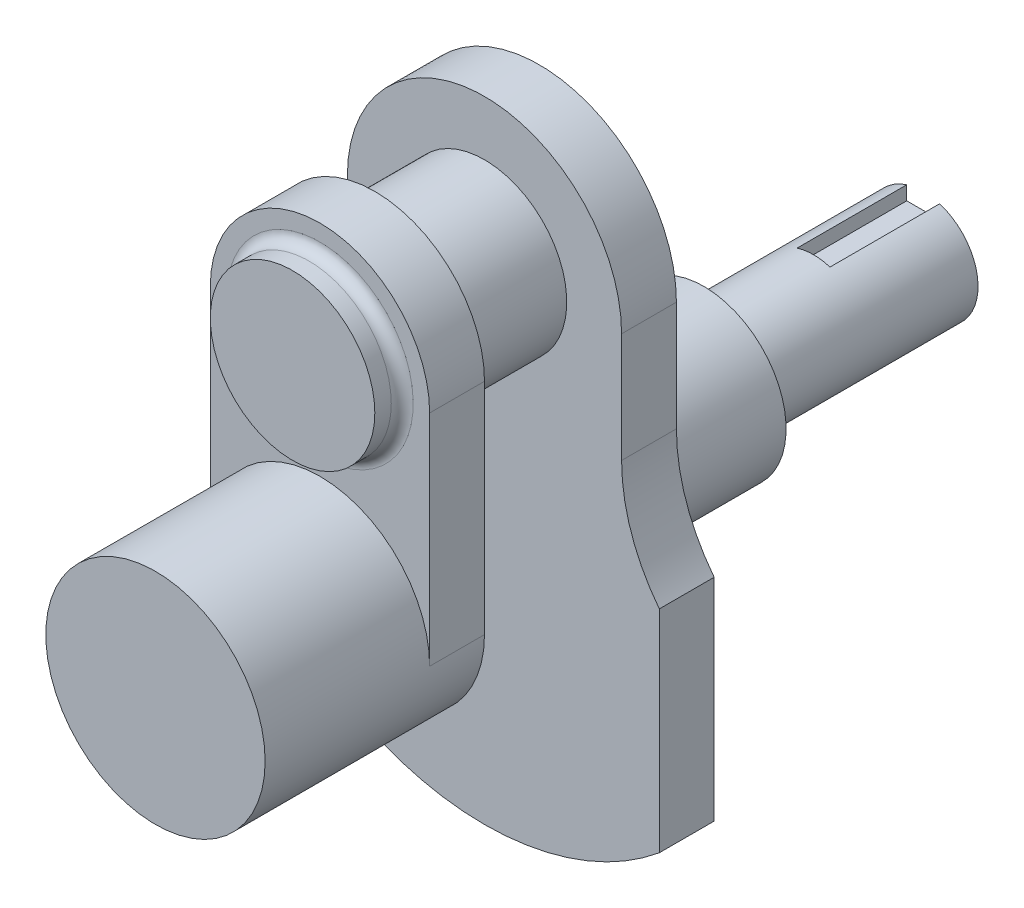
SolidWorks part; units mm, degrees
ref_plane "Ön Düzlem" through (0, 0, 0) normal (0, 0, 1) x (1, 0, 0)
ref_plane "Üst Düzlem" through (0, 0, 0) normal (0, 1, 0) x (1, 0, 0)
ref_plane "Sağ Düzlem" through (0, 0, 0) normal (1, 0, 0) x (0, 0, -1)
sketch "Çizim1" plane through (0, 0, 0) normal (0, 0, 1) x (1, 0, 0)
  line L0 (0, 0) -> (-40, 0)
  line L1 (-40, 0) -> (-40, 40)
  line L2 (-40, 40) -> (0, 40)
  line L3 (0, 40) -> (0, 0)
  dimension "D1" = 40
  dimension "D2" = 40
extrude "Yükseklik-Ekstrüzyon1" add sketch "Çizim1" along normal mid plane 40
sketch "Çizim3" plane through (0, 0, 20) normal (0, 0, 1) x (1, 0, 0)
  line L0 (-20, 40) -> (-20, 0) construction
  line L1 (0, 40) -> (-40, 40) construction
  line L2 (-40, 0) -> (0, 0) construction
  line L3 (0, 0) -> (0, 40) construction
  line L4 (-40, 40) -> (-40, 0) construction
  line L5 (-40, 0) -> (0, 0)
  line L6 (0, 0) -> (0, 40)
  line L7 (0, 40) -> (-40, 40)
  line L8 (-40, 40) -> (-40, 0)
  circle A0 centre (-20, 20) radius 20
  line M1 (0, 0) -> (0, 40)
  line M2 (0, 40) -> (-40, 40)
  line M3 (-40, 40) -> (-40, 0)
  line M4 (-40, 0) -> (0, 0)
  dimension "D1" = 40
extrude "Kes-Ekstrüzyon1" cut sketch "Çizim3" against normal blind 40 contours A0 L7 M3 | A0 L6 M2 | A0 L5 M1 | A0 L8 M4 region at (-35.5326, 4.4674, 20) region at (-4.4674, 4.4674, 20) region at (-35.5326, 35.5326, 20) region at (-4.4674, 35.5326, 20)
sketch "Çizim4" plane through (0, 0, 0) normal (1, 0, 0) x (0, 0, -1)
  line L0 (-20, 20) -> (20, 20) construction
  line L1 (-20, 40) -> (-20, 0) construction
  line L2 (20, 0) -> (20, 40) construction
  line L3 (10, 20) -> (10, 85)
  line L4 (10, 85) -> (20, 85)
  line L5 (20, 85) -> (20, 20)
  line L6 (10, 20) -> (20, 20)
  dimension "D1" = 10
  dimension "D2" = 65
extrude "Yükseklik-Ekstrüzyon2" add sketch "Çizim4" against normal blind 40
sketch "Çizim7" plane through (0, 0, -10) normal (0, 0, 1) x (1, 0, 0)
  line L0 (-20, 20) -> (-20, 60) construction
  line L1 (-40, 60) -> (0, 60) construction
  line L2 (0, 85) -> (0, 20) construction
  line L3 (-40, 85) -> (0, 85) construction
  line L4 (-40, 85) -> (-40, 20) construction
  line L5 (0, 85) -> (0, 20)
  line L6 (-40, 85) -> (0, 85)
  line L7 (-40, 85) -> (-40, 20)
  circle A0 centre (-20, 20) radius 20 construction
  arc A1 (0, 20) -> (-40, 20) centre (-20, 20) ccw construction
  circle A2 centre (-20, 20) radius 20
  arc A3 (0, 20) -> (-40, 20) centre (-20, 20) ccw
  circle A4 centre (-20, 60) radius 20
  line M2 (-40, 85) -> (-40, 20)
  line M5 (0, 85) -> (-40, 85)
  dimension "D2" = 40
  dimension "D1" = 40
extrude "Kes-Ekstrüzyon2" cut sketch "Çizim7" against normal blind 40 contours A4 L5 M5 M2 region at (-0.4717, 72.5, -10)
sketch "Çizim8" plane through (0, 0, -10) normal (0, 0, 1) x (1, 0, 0)
  circle A0 centre (-20, 60) radius 15
  dimension "D1" = 30
extrude "Yükseklik-Ekstrüzyon3" add sketch "Çizim8" along normal blind 5 and the other way blind 30
fillet "Radyus1" radius 2 1 edges at (-20, 45, -10)
sketch "Çizim10" plane through (0, 0, -40) normal (0, 0, -1) x (-1, 0, 0)
  line L0 (-5, 60) -> (45, 60)
  line L1 (20, 60) -> (20, 20) construction
  line L2 (-5, 60) -> (-5, 40)
  line L3 (45, 60) -> (45, 40)
  line L4 (20, 20) -> (-37.5, 20) construction
  line L5 (-37.5, 20) -> (-37.5, 40) construction
  line L6 (20, 20) -> (-20, 20) construction
  line L7 (-20, 20) -> (-20, 40) construction
  line L8 (-20, 40) -> (-5, 40) construction
  line L9 (-11.8826, 20) -> (-11.8826, -18.5162)
  line L10 (51.8826, 20) -> (51.8826, -18.5162)
  arc A0 (45, 60) -> (-5, 60) centre (20, 60) ccw
  arc A1 (-11.8826, 20) -> (-5, 40) centre (-37.5, 40) ccw
  arc A2 (-11.8826, -18.5162) -> (51.8826, -18.5162) centre (20, 20) ccw
  arc A3 (51.8826, 20) -> (45, 40) centre (77.5, 40) cw
  circle A4 centre (20, 60) radius 15
  circle M1 centre (20, 60) radius 15
  dimension "D1" = 50
  dimension "D7" = 40
  dimension "D8" = 100
  dimension "D4" = 30
  dimension "D2" = 40
  dimension "D3" = 20
  dimension "D5" = 57.5
  dimension "D6" = 20
extrude "Yükseklik-Ekstrüzyon4" add sketch "Çizim10" along normal blind 10 separate body contours L0 A0 M1 | L10 A3 L3 L0 L2 A1 L9 A2 M1 region at (-20, 75.559, -40) region at (-20, 11.395, -40)
extrude "Yükseklik-Ekstrüzyon5" add sketch "Çizim10<3>" along normal blind 10 contours L0 M1 | L0 M1 region at (-20, 53.6338, -40) region at (-20, 66.3662, -40)
sketch "Çizim10<3>" plane through (0, 0, -40) normal (0, 0, -1) x (-1, 0, 0) same geometry as "Çizim10"
sketch "Çizim16" plane through (0, 0, 20) normal (0, 0, 1) x (1, 0, 0)
  point P0 (-20, 20)
  point P1 (0, 0)
  point P3 (-20, 20)
  point P4 (0, 0)
  point P5 (0, 0)
sketch "Çizim18" plane through (0, 0, -50) normal (0, 0, -1) x (-1, 0, 0)
  circle A0 centre (20, 20) radius 15
  dimension "D1" = 30
extrude "Yükseklik-Ekstrüzyon6" add sketch "Çizim18" along normal blind 30
sketch "Çizim19" plane through (0, 0, -80) normal (0, 0, -1) x (-1, 0, 0)
  circle A0 centre (20, 20) radius 10
  dimension "D1" = 20
extrude "Yükseklik-Ekstrüzyon7" add sketch "Çizim19" along normal blind 40
fillet "Radyus2" radius 2 1 edges at (-35, 20, -50)
fillet "Radyus3" radius 2 1 edges at (-30, 20, -80)
sketch "Çizim21" plane through (0, 0, -120) normal (0, 0, -1) x (-1, 0, 0)
  circle A0 centre (20, 20) radius 1
  dimension "D1" = 2
extrude "Kes-Ekstrüzyon3" cut sketch "Çizim21" against normal blind 20
sketch "Çizim22" plane through (0, 0, -120) normal (0, 0, -1) x (-1, 0, 0)
  line L0 (20, 20) -> (20, 27) construction
  line L1 (20, 27) -> (17, 27)
  line L2 (17, 27) -> (17, 29.5394)
  line L3 (20, 27) -> (23, 27)
  line L4 (23, 27) -> (23, 29.5394)
  circle A0 centre (20, 20) radius 10 construction
  circle A1 centre (20, 20) radius 10
  circle A2 centre (20, 20) radius 10 construction
  point P10 (17, 29.5394)
  circle M3 centre (20, 20) radius 10
  dimension "D1" = 7
  dimension "D2" = 3
  dimension "D3" = 3
extrude "Kes-Ekstrüzyon4" cut sketch "Çizim22" against normal blind 20 contours L3 L4 L2 L1 M3 region at (-20, 28.4272, -120)
